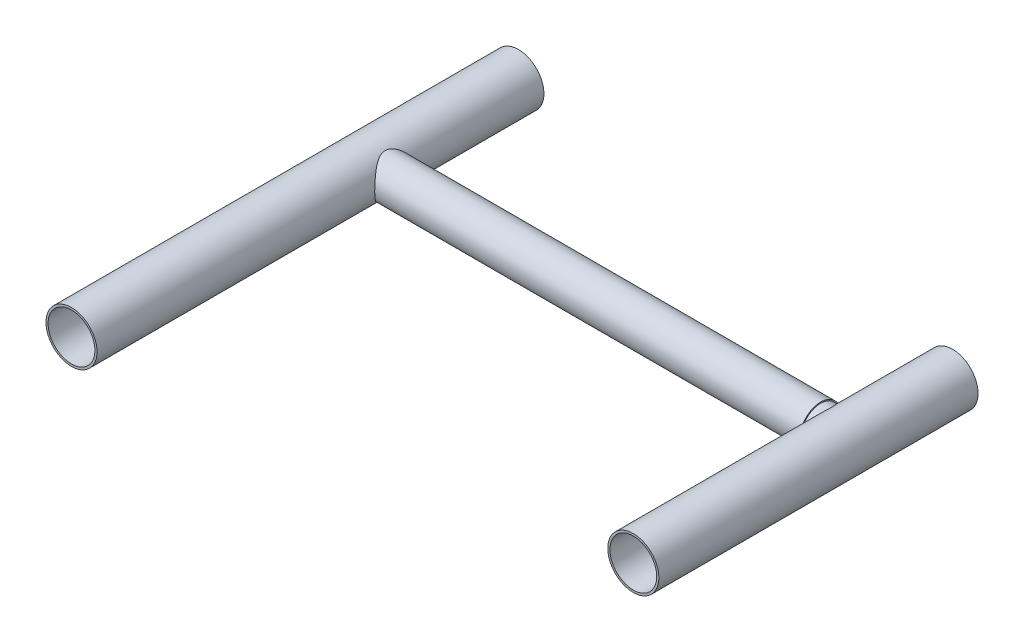
SolidWorks part; units mm, degrees
ref_plane "前视基准面" through (0, 0, 0) normal (0, 0, 1) x (1, 0, 0)
ref_plane "上视基准面" through (0, 0, 0) normal (0, 1, 0) x (1, 0, 0)
ref_plane "右视基准面" through (0, 0, 0) normal (1, 0, 0) x (0, 0, -1)
sketch "草图1" plane through (0, 0, 0) normal (0, 0, 1) x (1, 0, 0)
  circle A0 centre (12, 0) radius 11
  circle A1 centre (12, 0) radius 12
  dimension "D1" = 22
  dimension "D2" = 24
  dimension "D3" = 12
extrude "凸台-拉伸1" add sketch "草图1" along normal blind 210
ref_plane "基准面1" through (24, 0, 0) normal (1, 0, 0) x (0, 0, -1)
sketch "草图2" plane through (24, 0, 0) normal (1, 0, 0) x (0, 0, -1)
  line L0 (0, 0) -> (-210, 0) construction
  line L1 (-210, 12) -> (-210, -12) construction
  circle A0 centre (-70, 0) radius 7.5
  circle A1 centre (-70, 0) radius 9.5
  dimension "D1" = 15
  dimension "D2" = 19
  dimension "D3" = 70
extrude "切除-拉伸1" cut sketch "草图2" against normal blind 12 contours A1
extrude "凸台-拉伸2" add sketch "草图2<3>" along normal blind 200 and the other way blind 11
sketch "草图2<3>" plane through (24, 0, 0) normal (1, 0, 0) x (0, 0, -1) same geometry as "草图2"
extrude "切除-拉伸2" cut sketch "草图1<2>" along normal blind 250 contours A0
sketch "草图1<2>" plane through (0, 0, 0) normal (0, 0, 1) x (1, 0, 0) same geometry as "草图1"
ref_plane "基准面2" through (0, 0, 70) normal (0, 0, -1) x (-1, 0, 0)
sketch "草图5" plane through (0, 0, 70) normal (0, 0, -1) x (-1, 0, 0)
  line L0 (-224, 9.5) -> (-224, -9.5) construction
  circle A0 centre (-236, 0) radius 12
  circle A1 centre (-236, 0) radius 11
  dimension "D1" = 24
  dimension "D3" = 22
  dimension "D2" = 12
extrude "凸台-拉伸3" add sketch "草图5" along normal blind 50 and the other way blind 100 separate body
sketch "草图6" plane through (224, 0, 0) normal (1, 0, 0) x (0, 0, -1)
  circle A1 centre (-70, 0) radius 9.5
extrude "切除-拉伸3" cut sketch "草图6" along normal blind 12
sketch "草图8" plane through (224, 0, 0) normal (1, 0, 0) x (0, 0, -1)
  circle A0 centre (-70, 0) radius 8
  circle A1 centre (-70, 0) radius 9
  dimension "D1" = 16
  dimension "D2" = 18
extrude "凸台-拉伸4" add sketch "草图8" along normal blind 12
sketch "草图9" plane through (0, 0, 20) normal (0, 0, -1) x (-1, 0, 0)
  circle A0 centre (-236, 0) radius 10
extrude "切除-拉伸4" cut sketch "草图9" against normal blind 97
